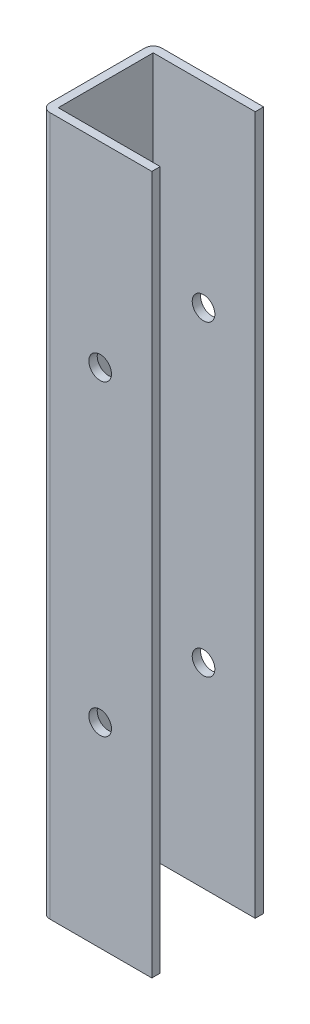
SolidWorks part; units mm, degrees
ref_plane "Спереди" through (0, 0, 0) normal (0, 0, 1) x (1, 0, 0)
ref_plane "Сверху" through (0, 0, 0) normal (0, 1, 0) x (1, 0, 0)
ref_plane "Справа" through (0, 0, 0) normal (1, 0, 0) x (0, 0, -1)
sketch "Эскиз1" plane through (0, 0, 0) normal (0, 1, 0) x (1, 0, 0)
  line L1 (-37, 20) -> (37, 20)
  line L2 (-40, 17) -> (-40, -17)
  line L3 (-37, -20) -> (37, -20)
  line L4 (40, 17) -> (40, -17)
  line L5 (-40, 20) -> (40, -20) construction
  line L6 (-40, -20) -> (40, 20) construction
  arc A0 (-37, 20) -> (-40, 17) centre (-37, 17) ccw
  arc A1 (-40, -17) -> (-37, -20) centre (-37, -17) ccw
  arc A2 (37, -20) -> (40, -17) centre (37, -17) ccw
  arc A3 (37, 20) -> (40, 17) centre (37, 17) cw
  point P0 (0, 0)
  dimension "D1" = 3
extrude "Вытянуть-Тонкостенный1" add sketch "Эскиз1" along normal blind 250 thin thin type one direction reverse wall 3
sketch "Эскиз2" plane through (0, 250, 0) normal (0, 1, 0) x (1, 0, 0)
  line L1 (-0.5, -21.5541) -> (41.1465, -21.5541)
  line L2 (-0.5, -21.5541) -> (-0.5, 20.9728)
  line L3 (-0.5, 20.9728) -> (41.1465, 20.9728)
  line L4 (41.1465, -21.5541) -> (41.1465, 20.9728)
extrude "Вырез-Вытянуть1" cut sketch "Эскиз2" against normal through all
sketch "Эскиз3" plane through (0, 0, -20) normal (0, 0, -1) x (-1, 0, 0)
  circle A0 centre (19, 180) radius 4.05
  circle A1 centre (19, 70) radius 4.05
  dimension "D1" = 2
extrude "Вырез-Вытянуть2" cut sketch "Эскиз3" against normal through all
